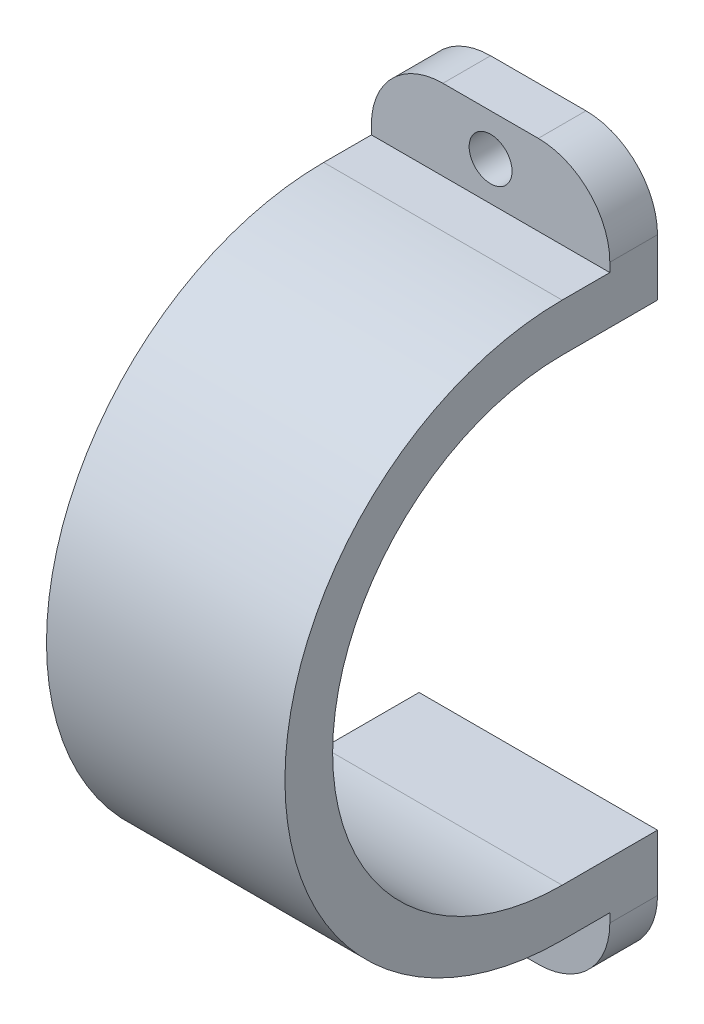
SolidWorks part; units mm, degrees
ref_plane "Top" through (0, 0, 0) normal (0, 0, 1) x (1, 0, 0)
ref_plane "Front" through (0, 0, 0) normal (0, 1, 0) x (1, 0, 0)
ref_plane "Right" through (0, 0, 0) normal (1, 0, 0) x (0, 0, -1)
sketch "Hold Down Bracket Sketch" plane through (0, 0, 0) normal (1, 0, 0) x (0, 0, -1)
  line L0 (-3, -19.25) -> (-3, 10.6262) construction
  line L1 (-33.5, -23.25) -> (-33.5, 23.25) construction
  line L2 (-33.5, -23.25) -> (-29.5, -23.25)
  line L3 (-29.5, -23.25) -> (-29.5, -30)
  line L4 (-29.5, -30) -> (-25.5, -30)
  line L5 (-25.5, -30) -> (-25.5, -19.25)
  line L6 (-25.5, -19.25) -> (-33.5, -19.25)
  line L7 (-33.5, 0) -> (0, 0) construction
  line L8 (-29.5, 30) -> (-25.5, 30)
  line L9 (-25.5, 19.25) -> (-33.5, 19.25)
  line L10 (-33.5, 23.25) -> (-29.5, 23.25)
  line L11 (-29.5, 23.25) -> (-29.5, 30)
  line L12 (-25.5, 30) -> (-25.5, 19.25)
  line L13 (-25, -30) -> (-25, 30) construction
  line L14 (-29.5, -23.25) -> (-29.5, -19.25) construction
  arc A0 (-33.5, 19.25) -> (-33.5, -19.25) centre (-33.5, 0) ccw
  arc A1 (-33.5, -23.25) -> (-33.5, 23.25) centre (-33.5, 0) cw
  dimension "D3" = 19.25
  dimension "Bottom Offset" = 3
  dimension "Center of Pump" = 30.5
  dimension "D1" = 4
  dimension "D2" = 30
  dimension "D4" = 0.5
  dimension "Cradle Height" = 25
extrude "Motor Clamp Extrude" add sketch "Hold Down Bracket Sketch" along normal blind 20 separate body
hole_wizard "Clamp Clearance Hole" positions "Sketch8" profile "Sketch9" hole size "M3" standard "ANSI Metric" end condition up to next
sketch "Sketch8" plane through (0, 0, 29.5) normal (0, 0, 1) x (1, 0, 0)
  line L5 (0, -26.5) -> (20, -26.5) construction
  line L6 (0, -30) -> (0, -23.25) construction
  line L7 (20, -23.25) -> (20, -30) construction
  line L9 (20, -30) -> (0, -30) construction
  point P0 (10, -26.5)
  dimension "Screw Position" = 3.5
sketch "Sketch9" plane through (10, -26.5, 29.5) normal (1, 0, 0) x (0, -1, 0)
  line L0 (0, 0) -> (0, 4)
  line L1 (0, 4) -> (1.8, 4)
  line L2 (1.8, 4) -> (1.8, 0)
  line L5 (1.8, 0) -> (0, 0)
  line L11 (0, -6.35) -> (0, 107.95) construction
  dimension "Thru Hole Dia." = 3.6
  dimension "Thru Hole Depth" = 4
mirror "Clamp Clearance Hole Mirror" about plane through (0, 0, 0) normal (0, 1, 0) of "Clamp Clearance Hole"
fillet "Clamp Corner Fillets" radius 6 4 edges at (20, 30, 27.5) (0, 30, 27.5) (0, -30, 27.5) (20, -30, 27.5)
equation "\"Clearance\"= 0.5mm"
equation "\"D2@Hold Down Bracket Sketch\"=\"Base Width\"/2"
equation "\"D4@Hold Down Bracket Sketch\"=\"Clearance\""
